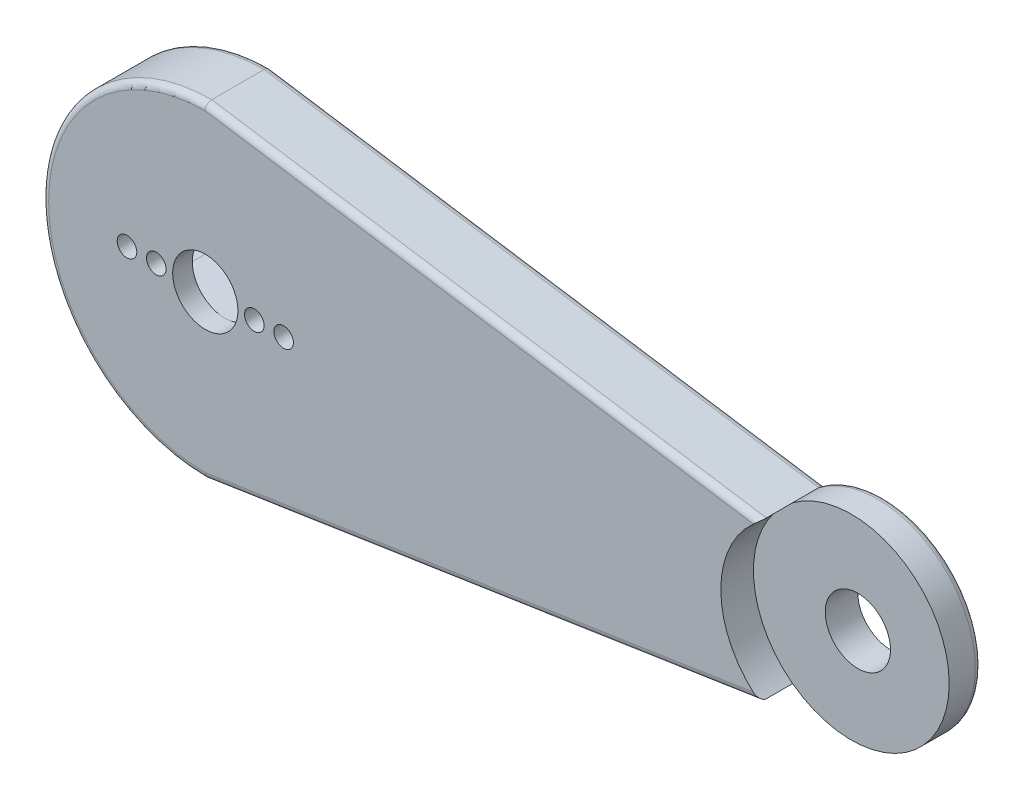
SolidWorks part; units mm, degrees
material "PP Copolymer"
ref_plane "Front Plane" through (0, 0, 0) normal (0, 0, 1) x (1, 0, 0)
ref_plane "Top Plane" through (0, 0, 0) normal (0, 1, 0) x (1, 0, 0)
ref_plane "Right Plane" through (0, 0, 0) normal (1, 0, 0) x (0, 0, -1)
sketch "Sketch1" plane through (0, 0, 0) normal (0, 0, 1) x (1, 0, 0)
  line L0 (0, 0) -> (155.5348, 0) construction
  line L1 (0, 25) -> (85, 12)
  line L2 (85, 12) -> (85, -12)
  line L3 (0, -25) -> (85, -12)
  circle A0 centre (0, 0) radius 25
  point P3 (0, -25)
  point P4 (0, 25)
  point P10 (85, 0)
  dimension "D1" = 50
  dimension "D2" = 12
  dimension "D3" = 85
extrude "Boss-Extrude1" add sketch "Sketch1" along normal blind 10 contours L1 A0 L3 | A0 L0 L2 L1 | L0 A0 L3 L2 region at (49.6745, 9.2066, 0) region at (-0.0056, 0, 0) region at (49.6745, -9.2066, 0)
sketch "Sketch2" plane through (0, 0, 10) normal (0, 0, 1) x (1, 0, 0)
  circle A0 centre (0, 0) radius 15
  dimension "D1" = 30
sketch "Sketch3" plane through (0, 0, 0) normal (0, 0, -1) x (-1, 0, 0)
  line L0 (0, 0) -> (54.7549, 0) construction
  line L1 (54.7549, 0) -> (-102.7825, 0) construction
  line L2 (0, 0) -> (0, -35.7393) construction
  line L3 (10, 0) -> (10, -7.545) construction
  line L4 (10, -7.545) -> (10, 4.8679) construction
  line L5 (10, -5) -> (-10, -5)
  line L6 (10, 5) -> (-10, 5)
  arc A0 (10, -5) -> (10, 5) centre (10, 0) ccw
  arc A1 (-10, -5) -> (-10, 5) centre (-10, 0) cw
  point P6 (10, -5)
  point P7 (10, 5)
  point P15 (0, 5)
  point P17 (0, -5)
  dimension "D1" = 5
  dimension "D2" = 10
extrude "Cut-Extrude2" cut sketch "Sketch3" against normal blind 7
sketch "Sketch4" plane through (0, 0, 7) normal (0, 0, -1) x (-1, 0, 0)
  line L0 (0, 0) -> (31.6701, 0) construction
  line L1 (0, 0) -> (0, -13.4811) construction
  circle A0 centre (12, 0) radius 1.5
  circle A1 centre (7.511, 0) radius 1.5
  circle A3 centre (0, 0) radius 5
  circle A4 centre (-7.511, 0) radius 1.5
  circle A5 centre (-12, 0) radius 1.5
  dimension "D1" = 3
  dimension "D2" = 3
  dimension "D3" = 10
  dimension "D5" = 12
  dimension "D4" = 7.511
extrude "Cut-Extrude4" cut sketch "Sketch4" against normal up to next
sketch "Sketch5" plane through (0, 0, 10) normal (0, 0, 1) x (1, 0, 0)
  line L0 (0, 0) -> (119.2593, 0) construction
  circle A0 centre (94, 0) radius 15
  dimension "D2" = 30
  dimension "D1" = 94
extrude "Boss-Extrude2" add sketch "Sketch5" against normal up to surface (10 mm away) up to face at (0, 0, 0)
sketch "Sketch8" plane through (0, 0, 10) normal (0, 0, 1) x (1, 0, 0)
  line L0 (0, 0) -> (133.1171, 0) construction
  line L1 (85, 12) -> (85, -12)
  circle A0 centre (94, 0) radius 15
  point P5 (85, 12)
  point P6 (85, -12)
  dimension "D2" = 30
  dimension "D1" = 94
extrude "Cut-Extrude7" cut sketch "Sketch8" against normal blind 5 contours L1 L0 A0 | L0 L1 | L0 A0 L1 | A0 L0 L1 region at (82.5534, 4.6502, 10) region at (82.5534, -4.6502, 10) region at (95.9003, 6.6511, 10) region at (95.9003, -6.6511, 10)
fillet "Fillet4" radius 1 7 edges at (-25, 0, 0) (109, 0, 0) (42.5, -18.5, 0) (42.5, 18.5, 0) (42.5, -18.5, 10) (-25, 0, 10) (42.5, 18.5, 10)
sketch "Sketch9" plane through (0, 0, 5) normal (0, 0, 1) x (1, 0, 0)
  circle A0 centre (95, 0) radius 5
  dimension "D2" = 10
  dimension "D1" = 95
extrude "Cut-Extrude8" cut sketch "Sketch9" against normal blind 10
sketch "Sketch10" plane through (0, 0, 0) normal (0, 0, -1) x (-1, 0, 0)
  line L0 (0, 0) -> (-95, 0) construction
ref_plane "Plane2" through (0, 0, 10) normal (0, 0, 1) x (1, 0, 0)
ref_plane "Plane3" through (0, 0, 0) normal (0, 0, -1) x (-1, 0, 0)
ref_plane "Plane4" through (0, 0, 0) normal (1, 0, 0) x (0, 0, -1)
sketch "Sketch15" plane through (0, 0, 0) normal (1, 0, 0) x (0, 0, -1)
  line L0 (-10, 0) -> (0, 0) construction
  point P4 (-5, 0)
ref_plane "Plane5" through (0, 0, 0) normal (0, 1, 0) x (1, 0, 0)
sketch "Sketch18" plane through (0, 0, 0) normal (0, 1, 0) x (1, 0, 0)
  line L0 (0, -5) -> (95, -5) construction
